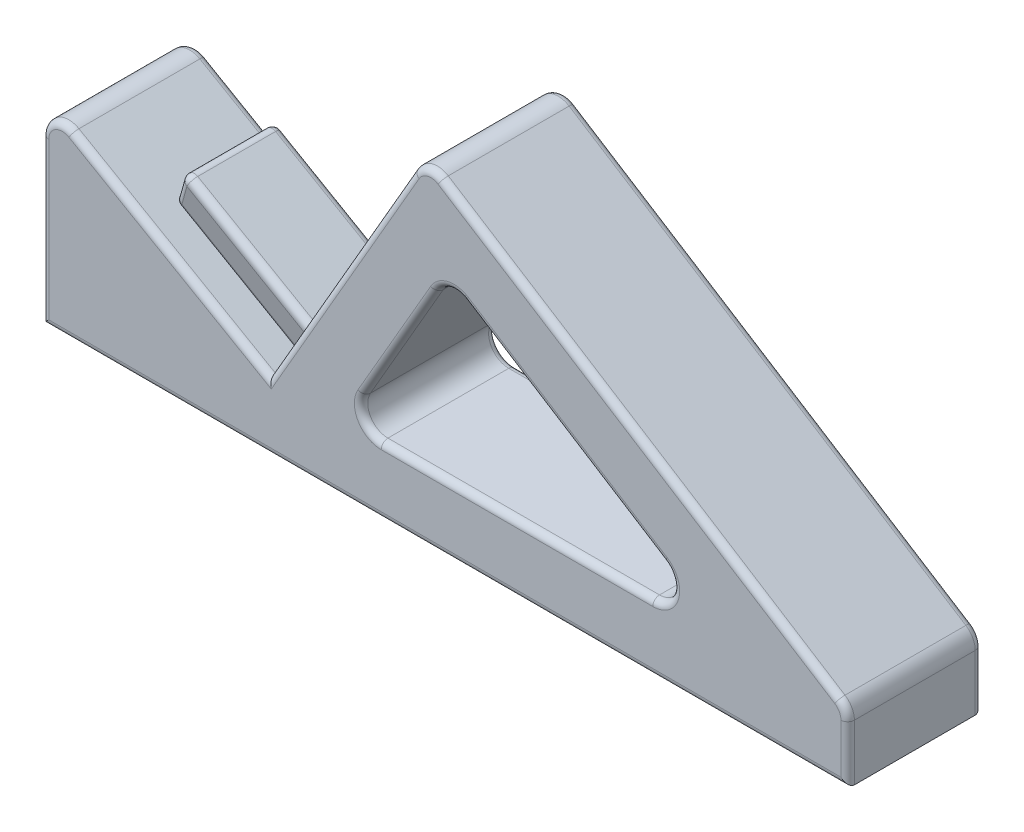
SolidWorks part; units mm, degrees
ref_plane "Plano frontal" through (0, 0, 0) normal (0, 0, 1) x (1, 0, 0)
ref_plane "Plano superior" through (0, 0, 0) normal (0, 1, 0) x (1, 0, 0)
ref_plane "Plano direito" through (0, 0, 0) normal (1, 0, 0) x (0, 0, -1)
sketch "Esboço1" plane through (0, 0, 0) normal (0, 0, 1) x (1, 0, 0)
  line L0 (60, 0) -> (-60, 0)
  line L1 (-60, 0) -> (-60, 29.5)
  line L2 (-60, 29.5) -> (-26.225, 10)
  line L3 (-26.225, 10) -> (-3.131, 50)
  line L4 (-3.131, 50) -> (60, 10)
  line L5 (60, 10) -> (60, 0)
  point P0 (-3.8157, 48.8141)
  point P4 (0, 0)
  dimension "D1" = 30
  dimension "D2" = 39
  dimension "D3" = 10
  dimension "D4" = 120
  dimension "D5" = 10
  dimension "D6" = 50
extrude "Ressalto-extrusão1" add sketch "Esboço1" along normal blind 20
sketch "Esboço2" plane through (-23.9989, 13.8558, 0) normal (-0.866, 0.5, 0) x (0, 0, 1)
  line L0 (5, -4.4523) -> (2.5, 2.5477) construction
  line L1 (20, -4.4523) -> (0, -4.4523) construction
  line L2 (2.5, 2.5477) -> (17.5, 2.5477) construction
  line L3 (17.5, 2.5477) -> (15, -4.4523) construction
  line L4 (15, -4.4523) -> (5, -4.4523) construction
  line L5 (20, -4.4523) -> (0, -4.4523) construction
  line L6 (5.1883, -4.385) -> (2.7838, 2.3477)
  line L7 (2.7838, 2.3477) -> (17.2162, 2.3477)
  line L8 (17.2162, 2.3477) -> (14.8117, -4.385)
  line L9 (14.8117, -4.385) -> (14.8117, -4.4523)
  line L10 (14.8117, -4.4523) -> (5.1883, -4.4523)
  line L11 (5.1883, -4.4523) -> (5.1883, -4.385)
  point P9 (10, -4.4523)
  dimension "D1" = 15
  dimension "D2" = 10
  dimension "D3" = 7
  dimension "D4" = 0.2
extrude "Ressalto-extrusão2" add sketch "Esboço2" along normal blind 22
sketch "Esboço3" plane through (0, 0, 20) normal (0, 0, 1) x (1, 0, 0)
  line L13 (-14.678, 10) -> (41.3159, 10)
  line L15 (41.3159, 10) -> (0.3191, 35.9757)
  line L16 (0.3191, 35.9757) -> (-14.678, 10)
  line L19 (-14.678, 10) -> (41.3159, 10)
  line L21 (41.3159, 10) -> (0.3191, 35.9757)
  line L22 (0.3191, 35.9757) -> (-14.678, 10)
  dimension "D1" = 10
extrude "Corte-extrusão1" cut sketch "Esboço3" against normal through all
fillet "Filete1" radius 3 6 edges at (-60, 29.5, 10) (-3.131, 50, 10) (60, 10, 10) (-14.678, 10, 10) (0.3191, 35.9757, 10) (41.3159, 10, 10)
fillet "Filete2" radius 1 34 edges at (-15.4595, 28.6464, 20) (-2.8126, 48.7059, 20) (29.0577, 29.6052, 20) (59.6284, 9.7955, 20) (60, 4.1747, 20) (0, 0, 20) (-60, 12.1519, 20) (-58.5, 26.9019, 20) (-40.8625, 18.451, 20) (-12.0799, 11.5, 20) (10.747, 10, 20) (33.857, 12.1641, 20) (17.7706, 24.9184, 20) (0.6375, 34.6816, 20) (-6.6619, 23.8842, 20) (0, 0, 0) (60, 4.1747, 0) (59.6284, 9.7955, 0) (29.0577, 29.6052, 0) (-2.8126, 48.7059, 0) (-15.4595, 28.6464, 0) (-40.8625, 18.451, 0) (-58.5, 26.9019, 0) (-60, 12.1519, 0) (-12.0799, 11.5, 0) (-6.6619, 23.8842, 0) (0.6375, 34.6816, 0) (17.7706, 24.9184, 0) (33.857, 12.1641, 0) (10.747, 10, 0) (-32.3513, 21.389, 2.7838) (-32.3513, 21.389, 17.2162) (-35.7177, 15.5583, 5.1883) (-35.7177, 15.5583, 14.8117)
fillet "Filete4" radius 1 7 edges at (-45.2252, 21.0907, 14.8311) (-43.86, 23.4554, 15.8002) (-42.0895, 26.5218, 16.6146) (-45.2252, 21.0907, 5.1689) (-43.86, 23.4554, 4.1998) (-42.0895, 26.5218, 3.3854) (-41.8776, 26.889, 10)
